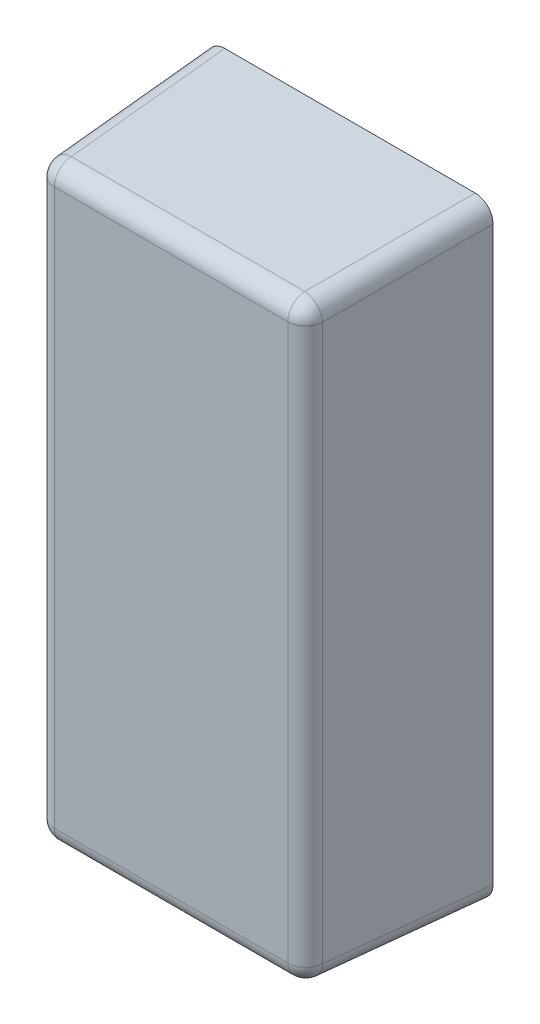
SolidWorks part; units mm, degrees
ref_plane "Plan de face" through (0, 0, 0) normal (0, 0, 1) x (1, 0, 0)
ref_plane "Plan de dessus" through (0, 0, 0) normal (0, 1, 0) x (1, 0, 0)
ref_plane "Plan de droite" through (0, 0, 0) normal (1, 0, 0) x (0, 0, -1)
sketch "Esquisse1" plane through (0, 0, 0) normal (0, 0, 1) x (1, 0, 0)
  line L1 (8, -17) -> (-8, -17)
  line L2 (8, -17) -> (8, 17)
  line L3 (8, 17) -> (-8, 17)
  line L4 (-8, -17) -> (-8, 17)
  line L5 (8, -17) -> (-8, 17) construction
  line L6 (8, 17) -> (-8, -17) construction
  point P0 (0, 0)
  dimension "D1" = 16
  dimension "D2" = 34
extrude "Boss.-Extru.1" add sketch "Esquisse1" along normal blind 10 draft 3
fillet "Congé1" radius 1 8 edges at (0, -16.4759, 10) (0, 16.4759, 10) (-7.4759, 0, 10) (7.4759, 0, 10) (7.738, 16.738, 5) (7.738, -16.738, 5) (-7.738, -16.738, 5) (-7.738, 16.738, 5)
shell "Coque1" thickness 1 removed face at (0, 0, 0)
sketch "Esquisse2" plane through (0, 0, 9) normal (0, 0, -1) x (-1, 0, 0)
  circle A0 centre (0, 0) radius 3
  circle A1 centre (0, 0) radius 1.5
  dimension "D1" = 6
  dimension "D2" = 3
extrude "Boss.-Extru.2" add sketch "Esquisse2" along normal up to surface (9 mm away) up to face at (0, 0, 0)
